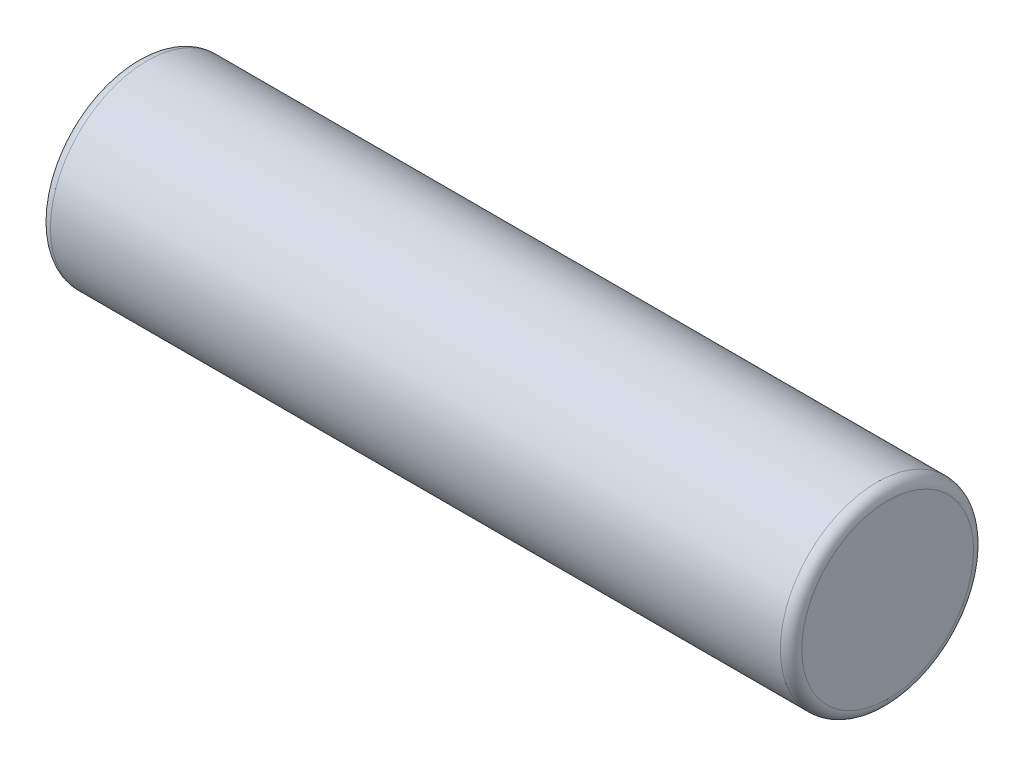
SolidWorks part; units mm, degrees
ref_plane "Front Plane" through (0, 0, 0) normal (0, 0, 1) x (1, 0, 0)
ref_plane "Top Plane" through (0, 0, 0) normal (0, 1, 0) x (1, 0, 0)
ref_plane "Right Plane" through (0, 0, 0) normal (1, 0, 0) x (0, 0, -1)
sketch "Sketch3" plane through (0, 0, 0) normal (0, 1, 0) x (1, 0, 0)
  line L1 (-35, -4.5) -> (35, -4.5)
  line L2 (-35, -4.5) -> (-35, 4.5)
  line L3 (-35, 4.5) -> (35, 4.5)
  line L4 (35, -4.5) -> (35, 4.5)
  line L5 (-35, -4.5) -> (35, 4.5) construction
  line L6 (-35, 4.5) -> (35, -4.5) construction
  point P0 (0, 0)
  dimension "D1" = 9
  dimension "D2" = 70
revolve "Revolve2" add sketch "Sketch3" angle 360 about L1
fillet "Fillet1" radius 1 2 edges at (35, 0, 13.5) (-35, 0, 13.5)
